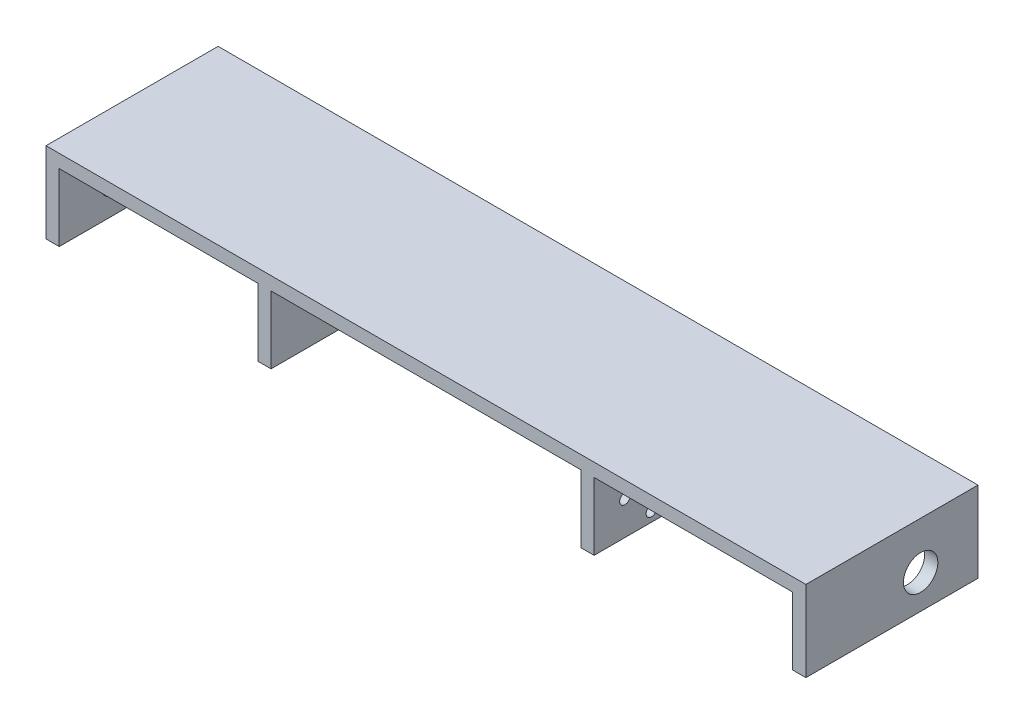
SolidWorks part; units mm, degrees
ref_plane "Front Plane" through (0, 0, 0) normal (0, 0, 1) x (1, 0, 0)
ref_plane "Top Plane" through (0, 0, 0) normal (0, 1, 0) x (1, 0, 0)
ref_plane "Right Plane" through (0, 0, 0) normal (1, 0, 0) x (0, 0, -1)
sketch "Sketch2" plane through (0, 0, 0) normal (0, 1, 0) x (1, 0, 0)
  line L1 (-42.6727, 74.2981) -> (244.3273, 74.2981)
  line L2 (-42.6727, 74.2981) -> (-42.6727, 9.2981)
  line L3 (-42.6727, 9.2981) -> (244.3273, 9.2981)
  line L4 (244.3273, 74.2981) -> (244.3273, 9.2981)
extrude "Boss-Extrude1" add sketch "Sketch2" along normal blind 5
sketch "Sketch4" plane through (0, 0, 0) normal (0, -1, 0) x (1, 0, 0)
  line L0 (-42.6727, -9.2981) -> (244.3273, -9.2981) construction
  line L1 (-42.6727, -74.2981) -> (-37.6727, -74.2981)
  line L2 (-42.6727, -74.2981) -> (-42.6727, -9.2981)
  line L3 (-42.6727, -9.2981) -> (-37.6727, -9.2981)
  line L4 (-37.6727, -74.2981) -> (-37.6727, -9.2981)
extrude "Boss-Extrude2" add sketch "Sketch4" along normal blind 25.5
sketch "Sketch5" plane through (0, 0, 0) normal (0, -1, 0) x (1, 0, 0)
  line L0 (-37.6727, -9.2981) -> (244.3273, -9.2981) construction
  line L1 (42.3273, -9.2981) -> (37.3273, -9.2981)
  line L2 (42.3273, -9.2981) -> (42.3273, -74.2981)
  line L3 (42.3273, -74.2981) -> (37.3273, -74.2981)
  line L4 (37.3273, -9.2981) -> (37.3273, -74.2981)
  line L5 (244.3273, -74.2981) -> (-37.6727, -74.2981) construction
  line L6 (-37.6727, -74.2981) -> (-37.6727, -9.2981) construction
  dimension "D1" = 80
  dimension "D2" = 5
extrude "Boss-Extrude3" add sketch "Sketch5" along normal blind 25.5 contours L2 L3 L4 L1
sketch "Sketch6" plane through (0, 0, 0) normal (0, -1, 0) x (1, 0, 0)
  line L0 (244.3273, -74.2981) -> (42.3273, -74.2981) construction
  line L1 (244.3273, -9.2981) -> (239.3273, -9.2981)
  line L2 (244.3273, -9.2981) -> (244.3273, -74.2981)
  line L3 (244.3273, -74.2981) -> (239.3273, -74.2981)
  line L4 (239.3273, -9.2981) -> (239.3273, -74.2981)
extrude "Boss-Extrude4" add sketch "Sketch6" along normal blind 25.5
sketch "Sketch7" plane through (-42.6727, 0, 0) normal (-1, 0, 0) x (0, 0, 1)
  line L0 (-9.2981, -25.5) -> (-74.2981, -25.5) construction
  line L1 (-9.2981, 5) -> (-9.2981, -25.5) construction
  circle A0 centre (-30.9648, -12.75) radius 6.5
  dimension "D1" = 12.75
  dimension "D2" = 21.6667
sketch "Sketch8" plane through (0, 0, 0) normal (0, -1, 0) x (1, 0, 0)
  line L0 (239.3273, -74.2981) -> (42.3273, -74.2981) construction
  line L1 (164.3273, -74.2981) -> (159.3273, -74.2981)
  line L2 (164.3273, -74.2981) -> (164.3273, -9.2981)
  line L3 (164.3273, -9.2981) -> (159.3273, -9.2981)
  line L4 (159.3273, -74.2981) -> (159.3273, -9.2981)
  line L5 (42.3273, -9.2981) -> (239.3273, -9.2981) construction
  line L6 (239.3273, -9.2981) -> (239.3273, -74.2981) construction
  dimension "D1" = 75
extrude "Boss-Extrude5" add sketch "Sketch8" along normal blind 25.5
sketch "Sketch9" plane through (244.3273, 0, 0) normal (1, 0, 0) x (0, 0, -1)
  line L0 (74.2981, 5) -> (74.2981, -25.5) construction
  line L1 (74.2981, -25.5) -> (9.2981, -25.5) construction
  circle A0 centre (52.6315, -12.75) radius 6.5
  dimension "D1" = 21.6667
  dimension "D2" = 12.75
extrude "Cut-Extrude1" cut sketch "Sketch7" against normal up to next
extrude "Cut-Extrude2" cut sketch "Sketch9" against normal up to next contours A0
sketch "Sketch10" plane through (37.3273, 0, 0) normal (-1, 0, 0) x (0, 0, 1)
  line L0 (-9.2981, -25.5) -> (-9.2981, 0) construction
  line L1 (-9.2981, -25.5) -> (-74.2981, -25.5) construction
  circle A0 centre (-30.9648, -12.75) radius 4.5
  dimension "D1" = 21.6667
  dimension "D2" = 12.75
sketch "Sketch11" plane through (164.3273, 0, 0) normal (1, 0, 0) x (0, 0, -1)
  line L0 (74.2981, -25.5) -> (74.2981, 0) construction
  line L1 (74.2981, -25.5) -> (9.2981, -25.5) construction
  circle A0 centre (52.6315, -12.75) radius 4.5
  dimension "D1" = 21.6667
  dimension "D2" = 12.75
extrude "Cut-Extrude3" cut sketch "Sketch11" against normal up to next
extrude "Cut-Extrude4" cut sketch "Sketch10" against normal up to next contours A0
sketch "Sketch14" plane through (159.3273, 0, 0) normal (-1, 0, 0) x (0, 0, 1)
  line L0 (-9.2981, -25.5) -> (-9.2981, 0) construction
  line L1 (-9.2981, -25.5) -> (-74.2981, -25.5) construction
  line L2 (-15.9681, -25.5) -> (-14.9681, -25.5)
  line L3 (-15.9681, -25.5) -> (-15.9681, 0)
  line L4 (-15.9681, 0) -> (-14.9681, 0)
  line L5 (-14.9681, -25.5) -> (-14.9681, 0)
  line L6 (-9.2981, 0) -> (-74.2981, 0) construction
  line L8 (-46.9681, -25.5) -> (-45.9681, -25.5)
  line L9 (-46.9681, -25.5) -> (-46.9681, 0)
  line L10 (-46.9681, 0) -> (-45.9681, 0)
  line L11 (-45.9681, -25.5) -> (-45.9681, 0)
  point P0 (-30.9681, -11.7464)
  dimension "D1" = 21.67
  dimension "D2" = 15
  dimension "D3" = 15
extrude "Boss-Extrude6" add sketch "Sketch14" along normal blind 1
sketch "Sketch15" plane through (159.3273, 0, 0) normal (-1, 0, 0) x (0, 0, 1)
  line L0 (-15.9681, 0) -> (-45.9681, 0) construction
  line L1 (-15.9681, 0) -> (-15.9681, -25.5) construction
  line L2 (-45.9681, -25.5) -> (-45.9681, 0) construction
  line L4 (-15.9681, -25.5) -> (-45.9681, -25.5) construction
  circle A0 centre (-20.9681, -12.75) radius 2
  circle A1 centre (-40.9681, -12.75) radius 2
  circle A2 centre (-30.9681, -21.75) radius 2
  circle A3 centre (-30.9681, -3.75) radius 2
  dimension "D2" = 5
  dimension "D3" = 5
  dimension "D4" = 15
  dimension "D6" = 3.75
  dimension "D7" = 4
  dimension "D1" = 12.75
  dimension "D5" = 3.75
extrude "Cut-Extrude6" cut sketch "Sketch15" against normal up to next
